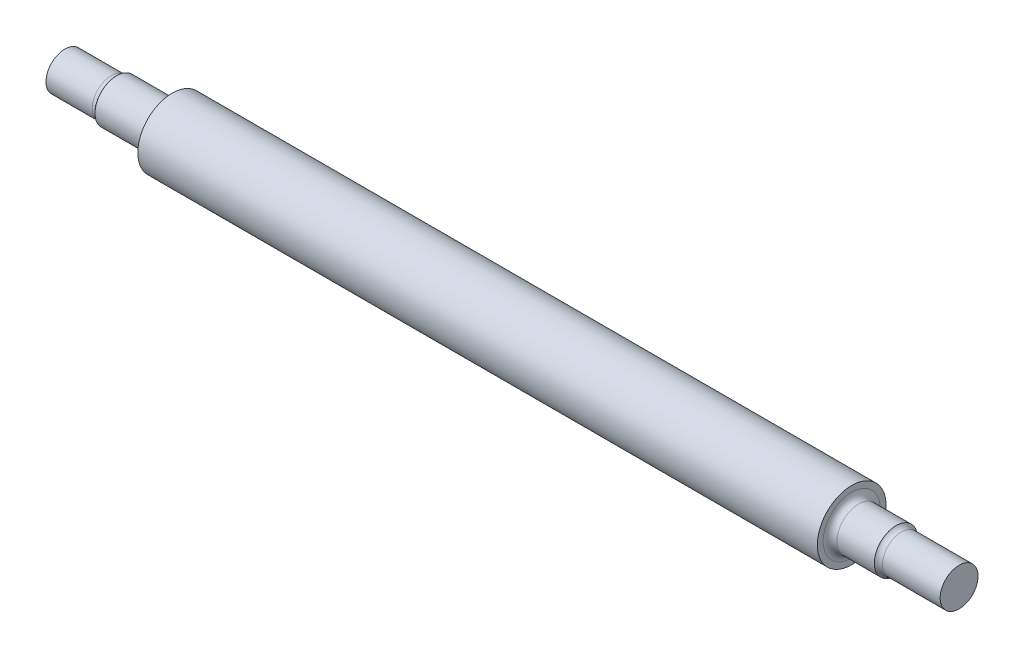
SolidWorks part; units mm, degrees
ref_plane "Front Plane" through (0, 0, 0) normal (0, 0, 1) x (1, 0, 0)
ref_plane "Top Plane" through (0, 0, 0) normal (0, 1, 0) x (1, 0, 0)
ref_plane "Right Plane" through (0, 0, 0) normal (1, 0, 0) x (0, 0, -1)
sketch "Sketch1" plane through (0, 0, 0) normal (0, 1, 0) x (1, 0, 0)
  line L0 (-77.4194, 0) -> (87.7419, 0) construction
  line L1 (-77.4194, 0) -> (-77.4194, 3.5)
  line L2 (-77.4194, 3.5) -> (-67.871, 3.5)
  line L3 (-67.871, 3.5) -> (-67.871, 4)
  line L4 (-67.871, 4) -> (-57.6087, 4)
  line L5 (-57.6087, 4) -> (-57.6087, 6.35)
  line L6 (-57.6087, 6.35) -> (67.9044, 6.35)
  line L7 (67.9044, 6.35) -> (67.9044, 4)
  line L8 (67.9044, 4) -> (76.0823, 4)
  line L9 (76.0823, 4) -> (76.0823, 3.5)
  line L10 (76.0823, 3.5) -> (87.7419, 3.5)
  line L11 (87.7419, 3.5) -> (87.7419, 0)
  dimension "D1" = 7
  dimension "D2" = 8
  dimension "D3" = 8
  dimension "D4" = 7
  dimension "D5" = 12.7
revolve "Revolve-Thin1" add sketch "Sketch1" angle 360 about L0
fillet "Fillet1" radius 1.27 4 edges at (-57.6087, 0, 4) (-67.871, 0, 3.5) (76.0823, 0, 3.5) (67.9044, 0, 4)
